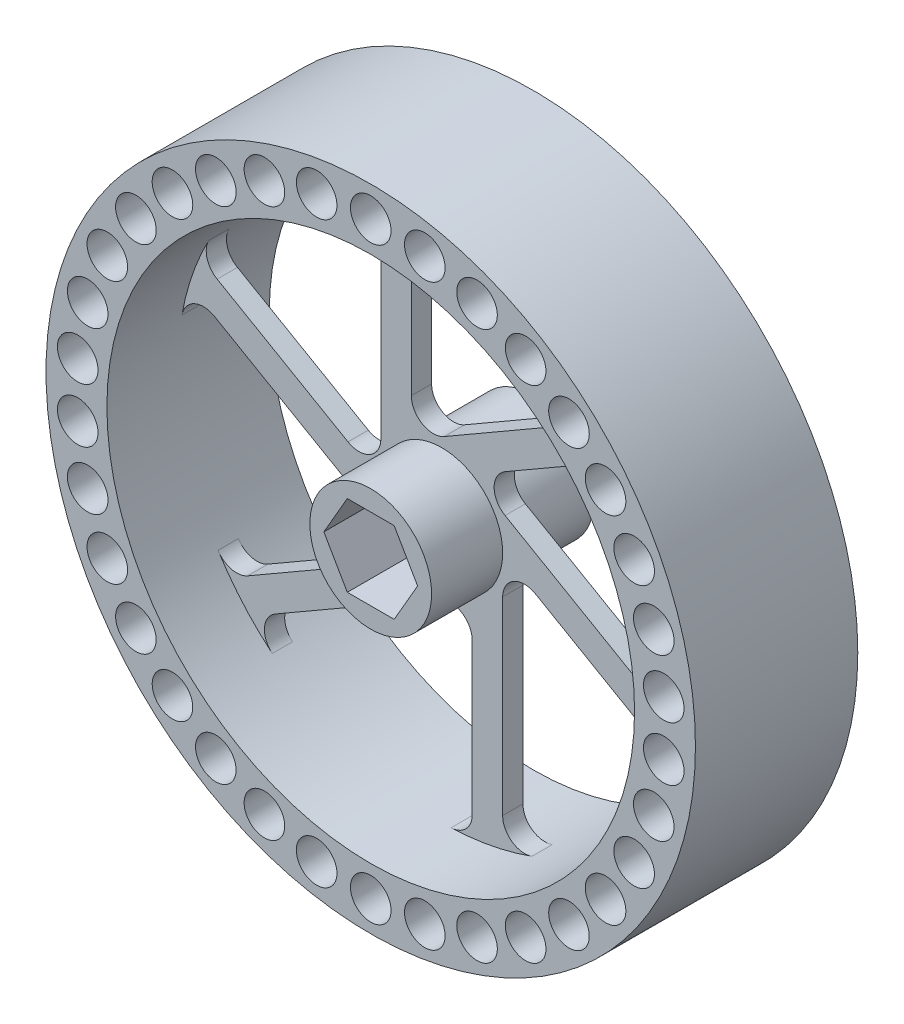
SolidWorks part; units mm, degrees
ref_plane "Front Plane" through (0, 0, 0) normal (0, 0, 1) x (1, 0, 0)
ref_plane "Top Plane" through (0, 0, 0) normal (0, 1, 0) x (1, 0, 0)
ref_plane "Right Plane" through (0, 0, 0) normal (1, 0, 0) x (0, 0, -1)
sketch "Sketch1" plane through (0, 0, 0) normal (0, 0, 1) x (1, 0, 0)
  line L1 (-3.6662, 6.35) -> (-7.3323, 0)
  line L2 (-7.3323, 0) -> (-3.6662, -6.35)
  line L3 (-3.6662, -6.35) -> (3.6662, -6.35)
  line L4 (3.6662, -6.35) -> (7.3323, 0)
  line L5 (7.3323, 0) -> (3.6662, 6.35)
  line L6 (3.6662, 6.35) -> (-3.6662, 6.35)
  circle A0 centre (0, 0) radius 6.35 construction
  circle A1 centre (0, 0) radius 46.0375 construction
  circle A2 centre (0, 0) radius 50.8
  dimension "D1" = 92.075
  dimension "D2" = 101.6
  dimension "D3" = 12.7
extrude "Boss-Extrude1" add sketch "Sketch1" along normal mid plane 25.4
sketch "Sketch2" plane through (0, 0, 12.7) normal (0, 0, 1) x (1, 0, 0)
  circle A0 centre (0, 46.0375) radius 3.175
  circle A1 centre (0, 0) radius 46.0375 construction
  dimension "D1" = 6.35
extrude "Cut-Extrude1" cut sketch "Sketch2" against normal through all
pattern_circular "CirPattern1" count 34 over 360 about axis through (0, 0, 12.7) along (0, 0, -1) of "Cut-Extrude1"
sketch "Sketch4" plane through (0, 0, 12.7) normal (0, 0, 1) x (1, 0, 0)
  circle A0 centre (0, 0) radius 41.275
  circle A1 centre (0, 0) radius 9.525
  dimension "D1" = 82.55
  dimension "D2" = 19.05
extrude "Cut-Extrude3" cut sketch "Sketch4" against normal through all
sketch "Sketch5" plane through (0, 0, 0) normal (0, 0, 1) x (1, 0, 0)
  line L0 (-9.525, 0) -> (-9.525, 40.1609)
  line L1 (-4.7625, 8.2489) -> (-4.7625, 40.9993)
  circle A0 centre (0, 0) radius 9.525 construction
  circle A1 centre (0, 0) radius 41.275 construction
  arc A2 (-4.7625, 40.9993) -> (-9.525, 40.1609) centre (0, 0) ccw
  arc A3 (-4.7625, 8.2489) -> (-9.525, 0) centre (0, 0) ccw
  dimension "D1" = 4.7625
extrude "Boss-Extrude2" add sketch "Sketch5" along normal mid plane 3.175
pattern_circular "CirPattern3" count 6 over 360 about axis through (0, 0, 12.7) along (0, 0, -1) of "Boss-Extrude2"
fillet "Fillet1" radius 3.429 18 edges at (37.8877, -16.3752, 0) (39.5429, -11.8316, 0) (33.1252, 24.6241, 0) (-9.525, 40.1609, 0) (30.0179, 28.3294, 0) (-4.7625, 40.9993, 0) (-39.5429, 11.8316, 0) (-37.8877, 16.3752, 0) (-33.1252, -24.6241, 0) (-30.0179, -28.3294, 0) (9.525, -40.1609, 0) (4.7625, -40.9993, 0) (-9.525, 0, 0) (-4.7625, -8.2489, 0) (4.7625, -8.2489, 0) (9.525, 0, 0) (4.7625, 8.2489, 0) (-4.7625, 8.2489, 0)
